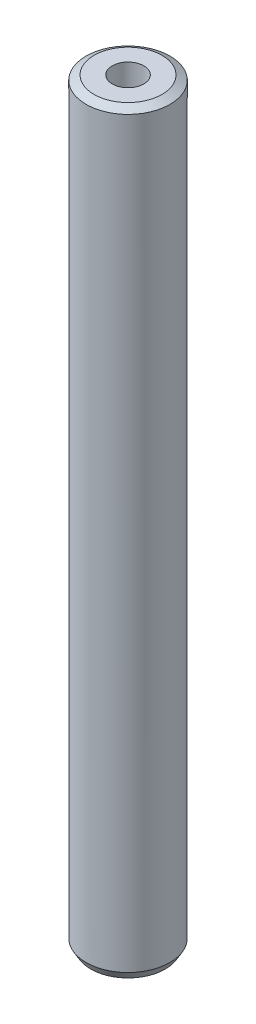
SolidWorks part; units mm, degrees
ref_plane "Front Plane" through (0, 0, 0) normal (0, 0, 1) x (1, 0, 0)
ref_plane "Top Plane" through (0, 0, 0) normal (0, 1, 0) x (1, 0, 0)
ref_plane "Right Plane" through (0, 0, 0) normal (1, 0, 0) x (0, 0, -1)
sketch "Sketch1" plane through (0, 0, 0) normal (0, 1, 0) x (1, 0, 0)
  circle A0 centre (0, 0) radius 10
  dimension "SHAFT_OD" = 20
extrude "Boss-Extrude1" add sketch "Sketch1" along normal blind 180.2826
sketch "Sketch2" plane through (0, 0, 0) normal (0, 1, 0) x (1, 0, 0)
  circle A0 centre (0, 0) radius 3.7597
  dimension "BORE_D" = 7.5194
extrude "Cut-Extrude1" cut sketch "Sketch2" along normal through all
chamfer "Chamfer1" distance 1.099 angle 60 2 edges at (0, 180.2826, 10) (0, 0, 10) first distance on face at (0, 180.2826, 10) first distance on face at (0, 0, 3.7597)
